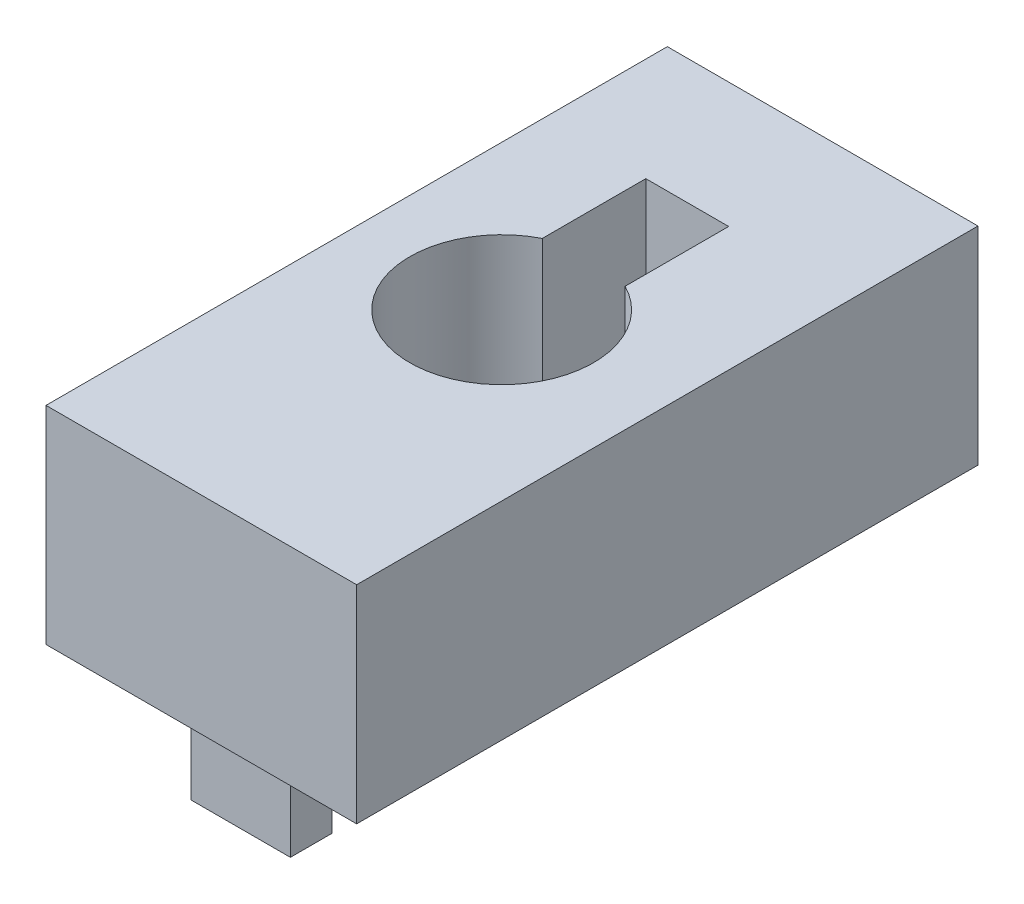
SolidWorks part; units mm, degrees
ref_plane "Front Plane" through (0, 0, 0) normal (0, 0, 1) x (1, 0, 0)
ref_plane "Top Plane" through (0, 0, 0) normal (0, 1, 0) x (1, 0, 0)
ref_plane "Right Plane" through (0, 0, 0) normal (1, 0, 0) x (0, 0, -1)
sketch "Sketch1" plane through (0, 0, 0) normal (0, 1, 0) x (1, 0, 0)
  line L0 (0, 0) -> (19.05, 0)
  line L1 (19.05, 0) -> (19.05, 19.05)
  line L2 (19.05, 19.05) -> (19.05, 38.1)
  line L3 (19.05, 38.1) -> (0, 38.1)
  line L4 (0, 38.1) -> (0, 19.05)
  line L5 (0, 19.05) -> (0, 0)
  point P5 (0, 0)
  point P8 (0, 19.05)
  dimension "D1" = 19.05
  dimension "D2" = 38.1
  dimension "D5" = 19.05
extrude "Boss-Extrude1" add sketch "Sketch1" along normal blind 12.7
ref_plane "MidPlane" through (0, 0, -19.05) normal (0, 0, -1) x (-1, 0, 0)
sketch "Sketch2" plane through (0, 12.7, 0) normal (0, -1, 0) x (1, 0, 0)
  line L0 (19.05, -38.1) -> (0, -38.1) construction
  line L1 (0, -38.1) -> (0, 0) construction
  line L2 (0, -6.985) -> (0, 6.985) construction
  line L3 (-6.985, -19.05) -> (6.985, -19.05) construction
  circle A0 centre (8.89, -19.05) radius 5.635
  point P7 (0, 0)
  point P10 (0, 0)
  dimension "D1" = 11.27
  dimension "D2" = 8.89
extrude "Haptic Motor Cutout" cut sketch "Sketch2" along normal blind 9.558 contours A0
sketch "Sketch3" plane through (0, 0, 0) normal (0, -1, 0) x (1, 0, 0)
  line L8 (11.43, -24.0801) -> (6.35, -24.0801)
  line L9 (11.43, -24.0801) -> (11.43, -30.4301)
  line L10 (6.35, -24.0801) -> (6.35, -30.4301)
  line L11 (11.43, -30.4301) -> (6.35, -30.4301)
  circle A3 centre (8.89, -19.05) radius 5.635 construction
  dimension "D1" = 5.08
  dimension "D2" = 6.35
extrude "Haptic Wire Cutout" cut sketch "Sketch3" against normal through all
sketch "Sketch4" plane through (0, 0, 0) normal (0, -1, 0) x (1, 0, 0)
  line L0 (19.05, -38.1) -> (0, -38.1) construction
  line L1 (13.716, -36.83) -> (7.62, -36.83)
  line L2 (13.716, -36.83) -> (13.716, -34.29)
  line L3 (13.716, -34.29) -> (7.62, -34.29)
  line L4 (7.62, -36.83) -> (7.62, -34.29)
  line L5 (0, -6.985) -> (0, 6.985) construction
  dimension "D1" = 2.54
  dimension "D2" = 6.096
  dimension "D3" = 1.27
  dimension "D4" = 7.62
extrude "Pins" add sketch "Sketch4" along normal blind 5.08
mirror "Mirror1" about plane through (0, 0, -19.05) normal (0, 0, -1) of "Pins"
ref_point "Point1" [suppressed]
ref_axis "Axis1" [suppressed] through (0, 12.7, -38.1) along (0, 0, 1)
sketch "Sketch5" [suppressed] plane through (0, 12.7, 0) normal (0, 1, 0) x (1, 0, 0)
  line L0 (0, 38.1) -> (0, 0) construction
  line L1 (0, 19.05) -> (25.4, 19.05) construction
equation "\"Arrow Height\"= 1.5in"
equation "\"Button Height\"= 2in"
equation "\"Button Width\"= 4in"
equation "\"Haptic Diameter\"= 10mm"
equation "\"Haptic Thickness\"= 2.7mm"
equation "\"D2@Sketch1\"=\"Arrow Height\""
equation "\"D5@Sketch1\"=\"Arrow Height\"/2"
equation "\"D1@Sketch2\"=\"Haptic Diameter\"+.05in"
equation "\"D1@Haptic Motor Cutout\"=\"Haptic Thickness\" + .02+.25"
equation "\"D1\"= \"Haptic Thickness\" + .02 + .25"
equation "\"Arrow Spacing\"= 1in"
equation "\"Arrow Width\"= 01in"
equation "\"Haptic Wire Angle\"= 63.43"
equation "\"Haptic Wire Width\"= .1in"
equation "\"Haptic Wire Height\"= .15in"
